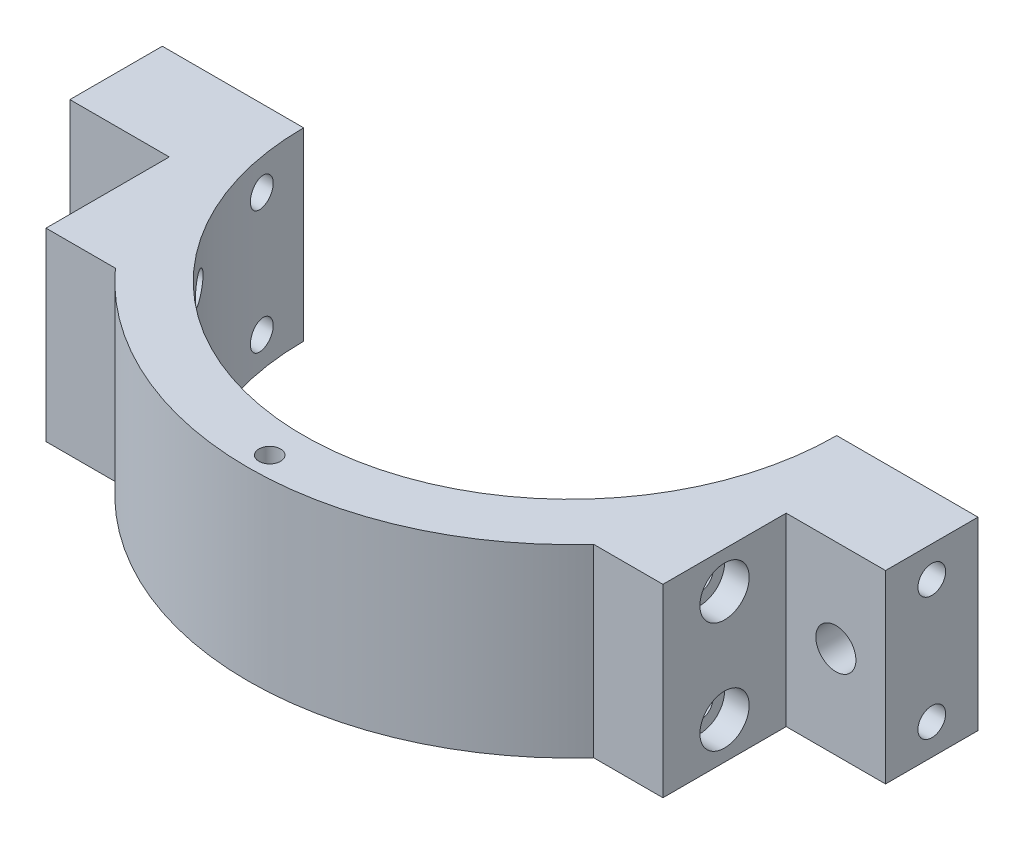
SolidWorks part; units mm, degrees
ref_plane "Front Plane" through (0, 0, 0) normal (0, 0, 1) x (1, 0, 0)
ref_plane "Top Plane" through (0, 0, 0) normal (0, 1, 0) x (1, 0, 0)
ref_plane "Right Plane" through (0, 0, 0) normal (1, 0, 0) x (0, 0, -1)
sketch "Sketch1" plane through (0, 0, 0) normal (0, 1, 0) x (1, 0, 0)
  line L0 (-43.25, 0) -> (-66.175, 0)
  line L4 (66.175, 0) -> (43.25, 0)
  line L5 (0, 0) -> (0, -67.037) construction
  line L6 (-66.175, 0) -> (-66.175, -15)
  line L7 (-66.175, -15) -> (-50.0506, -15)
  line L8 (66.175, -15) -> (50.0506, -15)
  line L9 (66.175, 0) -> (66.175, -15)
  circle A0 centre (0, 0) radius 43.25 construction
  arc A1 (-43.25, 0) -> (43.25, 0) centre (0, 0) ccw
  arc A2 (-50.0506, -15) -> (50.0506, -15) centre (0, 0) ccw
  dimension "D1" = 86.5
  dimension "D2" = 52.25
  dimension "D3" = 15
  dimension "D4" = 132.35
extrude "Boss-Extrude1" add sketch "Sketch1" along normal mid plane 30
sketch "Sketch2" plane through (0, 0, 15) normal (0, 0, 1) x (1, 0, 0)
  line L0 (-58.1128, -15) -> (-58.1128, 15) construction
  line L1 (-66.175, -15) -> (-50.0506, -15) construction
  line L2 (-66.175, 15) -> (-50.0506, 15) construction
  line L3 (0, 0) -> (0, 15) construction
  line L4 (50.0506, 15) -> (-50.0506, 15) construction
  circle A0 centre (-58.1128, 0) radius 3.25
  circle A1 centre (58.1128, 0) radius 3.25
  dimension "D1" = 6.5
extrude "Cut-Extrude1" cut sketch "Sketch2" against normal through all
sketch "Sketch3" plane through (-66.175, 0, 0) normal (-1, 0, 0) x (0, 0, 1)
  line L0 (7.5, 15) -> (7.5, -15) construction
  line L1 (0, 15) -> (15, 15) construction
  line L2 (0, -15) -> (15, -15) construction
  line L3 (15, 0) -> (0, 0) construction
  line L4 (15, 15) -> (15, -15) construction
  circle A0 centre (7.5, -10) radius 2.25
  circle A1 centre (7.5, 10) radius 2.25
  dimension "D1" = 20
  dimension "D2" = 4.5
extrude "Cut-Extrude2" cut sketch "Sketch3" against normal through all
sketch "Sketch4" plane through (0, 15, 0) normal (0, 1, 0) x (1, 0, 0)
  circle A0 centre (0, -48.75) radius 1.75
  arc A1 (-43.25, 0) -> (43.25, 0) centre (0, 0) ccw construction
  arc A2 (-50.0506, -15) -> (50.0506, -15) centre (0, 0) ccw construction
  point P2 (0, -43.25)
  point P9 (0, -52.25)
  dimension "D1" = 3.5
extrude "Cut-Extrude3" cut sketch "Sketch4" against normal through all both and the other way through all contours A0
sketch "Sketch5" plane through (0, 15, 0) normal (0, 1, 0) x (1, 0, 0)
  line L0 (-50.0506, -15) -> (-50.0506, -35)
  line L1 (-50.0506, -35) -> (-38.7951, -35)
  arc A0 (-50.0506, -15) -> (50.0506, -15) centre (0, 0) ccw construction
  arc A1 (-50.0506, -15) -> (-38.7951, -35) centre (0, 0) ccw
  dimension "D1" = 20
extrude "Boss-Extrude2" add sketch "Sketch5" against normal up to surface (30 mm away) up to face at (0, -15, 50.5)
ref_plane "Plane1" through (0, 0, 0) normal (-1, 0, 0) x (0, 0, 1)
mirror "Mirror1" about plane through (0, 0, 0) normal (-1, 0, 0) of "Boss-Extrude2"
hole_wizard "CBORE for M4 SHCS1" positions "Sketch9" profile "Sketch10" counterbore size "M4" standard "ANSI Metric"
sketch "Sketch9" plane through (50.0506, 484.7242, 401.677) normal (1, 0, 0) x (0, -0.9859, 0.1676)
  line L0 (405.8768, 451.0689) -> (423.6223, 454.0852) construction
  line L2 (414.7496, 452.577) -> (416.4253, 442.7184) construction
  circle A0 centre (405.8768, 451.0689) radius 2.25
  circle A1 centre (423.6223, 454.0852) radius 2.25
  point P0 (405.8768, 451.0689)
  point P2 (423.6223, 454.0852)
sketch "Sketch10" plane through (50.0506, 9, 25) normal (0, 1, 0) x (0, 0, -1)
  line L0 (0, 0) -> (0, 101.393)
  line L1 (0, 101.393) -> (2.15, 100.1012)
  line L2 (2.15, 100.1012) -> (2.15, 4)
  line L3 (2.15, 4) -> (4, 4)
  line L4 (4, 4) -> (4, 0)
  line L5 (4, 0) -> (0, 0)
  line L6 (0, 101.393) -> (-2.15, 100.1012) construction
  line L7 (0, -6.35) -> (0, 107.95) construction
  dimension "Hole Dia." = 4.3
  dimension "Hole Depth" = 100.1012
  dimension "C'Bore Dia." = 8
  dimension "C'Bore Depth" = 4
  dimension "Drill Angle" = 118
